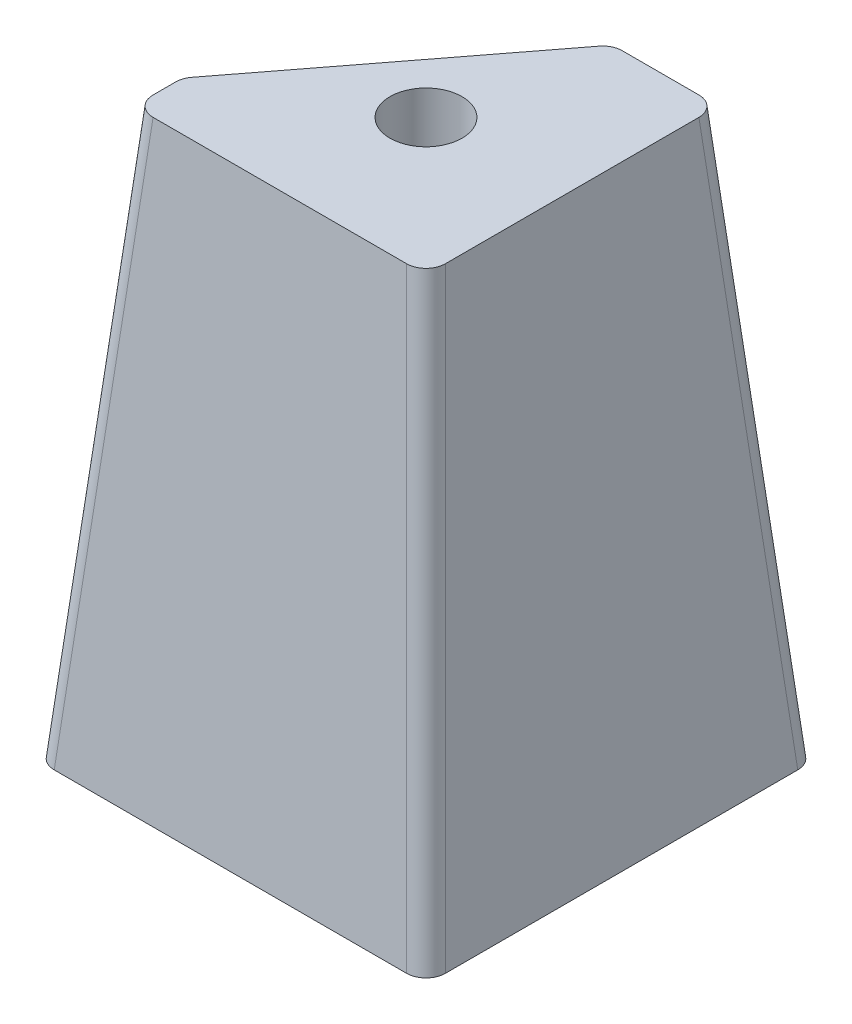
SolidWorks part; units mm, degrees
ref_plane "Front Plane" through (0, 0, 0) normal (0, 0, 1) x (1, 0, 0)
ref_plane "Top Plane" through (0, 0, 0) normal (0, 1, 0) x (1, 0, 0)
ref_plane "Right Plane" through (0, 0, 0) normal (1, 0, 0) x (0, 0, -1)
sketch "Sketch1" plane through (0, 0, 0) normal (0, 1, 0) x (1, 0, 0)
  line L0 (-4.5796, -4.7013) -> (4.9946, 7.7987)
  line L1 (4.9946, 7.7987) -> (10.4204, 7.7987)
  line L2 (10.4204, 7.7987) -> (10.4204, -7.2013)
  line L3 (10.4204, -7.2013) -> (-4.5796, -7.2013)
  line L4 (-4.5796, -7.2013) -> (-4.5796, -4.7013)
  dimension "D1" = 15
  dimension "D2" = 15
  dimension "D4" = 2.5
  dimension "D5" = 142.55
extrude "Boss-Extrude1" add sketch "Sketch1" along normal blind 29
sketch "Sketch2" plane through (0, 0, 0) normal (0, -1, 0) x (1, 0, 0)
  line L0 (-4.5796, 4.7013) -> (-4.5796, 7.2013) construction
  line L1 (10.4204, 7.2013) -> (10.4204, -7.7987) construction
  line L2 (-4.5796, 7.2013) -> (10.4204, 7.2013) construction
  circle A0 centre (-0.5796, 2.2013) radius 1.5
  circle A1 centre (7.4204, 2.2013) radius 2
  dimension "D1" = 3
  dimension "D3" = 4
  dimension "D2" = 4
  dimension "D4" = 3
  dimension "D5" = 5
  dimension "D6" = 5
extrude "Cut-Extrude1" cut sketch "Sketch2" against normal blind 10
sketch "Sketch3" plane through (0, 29, 0) normal (0, 1, 0) x (1, 0, 0)
  line L0 (10.4204, -7.2013) -> (10.4204, 7.7987) construction
  line L1 (-4.5796, -7.2013) -> (10.4204, -7.2013) construction
  circle A0 centre (3.4204, -0.2013) radius 1.85
  dimension "D1" = 3.7
  dimension "D2" = 7
  dimension "D3" = 7
extrude "Cut-Extrude2" cut sketch "Sketch3" against normal blind 12
draft "Draft1" type of draft neutral plane draft angle 5 faces to draft 5 face at (7.7075, 14.5, -7.7987) face at (10.4204, 14.5, -0.2987) face at (2.9204, 14.5, 7.2013) face at (-4.5796, 14.5, 5.9513) face at (0.2075, 14.5, -1.5487) neutral plane through (0, 29, 0) neutral plane normal (0, 1, 0) parameters "D1"=5
fillet "Fillet1" radius 1 5 edges at (4.3683, 14.5, -9.0673) (-5.8482, 14.5, 4.2713) (11.6889, 14.5, -9.0673) (11.6889, 14.5, 8.4699) (-5.8482, 14.5, 8.4699)
